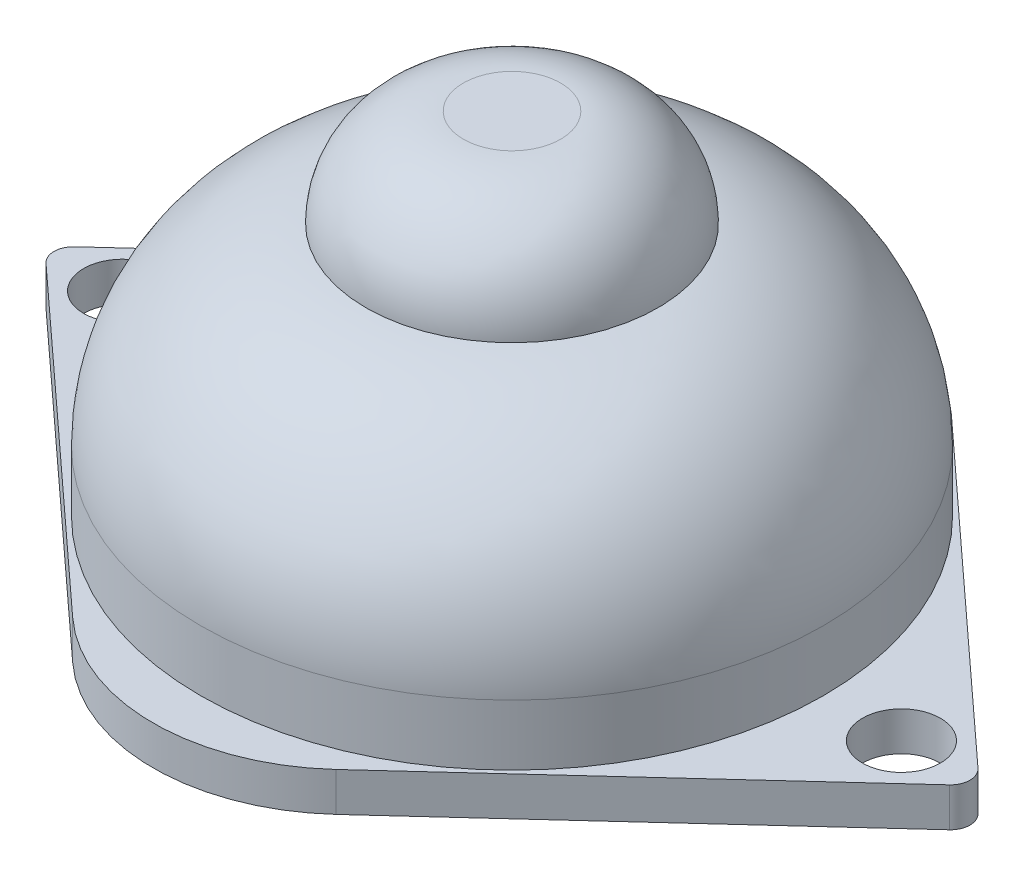
SolidWorks part; units mm, degrees
ref_plane "Front Plane" through (0, 0, 0) normal (0, 0, 1) x (1, 0, 0)
ref_plane "Top Plane" through (0, 0, 0) normal (0, 1, 0) x (1, 0, 0)
ref_plane "Right Plane" through (0, 0, 0) normal (1, 0, 0) x (0, 0, -1)
sketch "Sketch1" plane through (0, 0, 0) normal (0, 1, 0) x (1, 0, 0)
  circle A0 centre (0, 0) radius 16
  point P3 (0, 0)
  dimension "D1" = 32
extrude "Boss-Extrude1" add sketch "Sketch1" along normal blind 13
sketch "Sketch2" plane through (0, 13, 0) normal (0, 1, 0) x (1, 0, 0)
  circle A0 centre (0, 0) radius 7.5
  dimension "D1" = 15
extrude "Boss-Extrude2" add sketch "Sketch2" along normal blind 5
fillet "Fillet3" radius 10 1 edges at (0, 13, 16)
fillet "Fillet4" radius 5 1 edges at (0, 18, 7.5)
sketch "Sketch3" plane through (0, 0, 0) normal (0, -1, 0) x (1, 0, 0)
  line L0 (0, 24.9426) -> (0, -26.3328) construction
  line L1 (-37.2912, 0) -> (43.5881, 0) construction
  line L2 (6.7572, 15.8059) -> (23.1958, 0.7372)
  line L7 (0, 23.9811) -> (0, -23.9811) construction
  line L8 (-24, 0) -> (24, 0) construction
  line L9 (6.7572, -15.8059) -> (23.1958, -0.7372)
  line L10 (37.2912, 0) -> (-43.5881, 0) construction
  line L11 (-6.7572, -15.8059) -> (-23.1958, -0.7372)
  line L12 (-6.7572, 15.8059) -> (-23.1958, 0.7372)
  circle A1 centre (20, 0) radius 2
  circle A2 centre (0, 0) radius 16 construction
  arc A3 (23.1958, -0.7372) -> (23.1958, 0.7372) centre (22.5201, 0) ccw
  arc A4 (-23.1958, -0.7372) -> (-23.1958, 0.7372) centre (-22.5201, 0) cw
  circle A5 centre (-20, 0) radius 2
  arc A6 (6.7572, 15.8059) -> (-6.7572, 15.8059) centre (0, 8.4343) ccw
  arc A7 (6.7572, -15.8059) -> (-6.7572, -15.8059) centre (0, -8.4343) cw
  point P7 (0, 0)
  point P24 (0, 22)
  point P27 (0, -22)
  dimension "D1" = 4
  dimension "D2" = 1
  dimension "D4" = 10
  dimension "D3" = 20
  dimension "D5" = 22
  dimension "D6" = 22
extrude "Boss-Extrude3" add sketch "Sketch3" along normal blind 2
